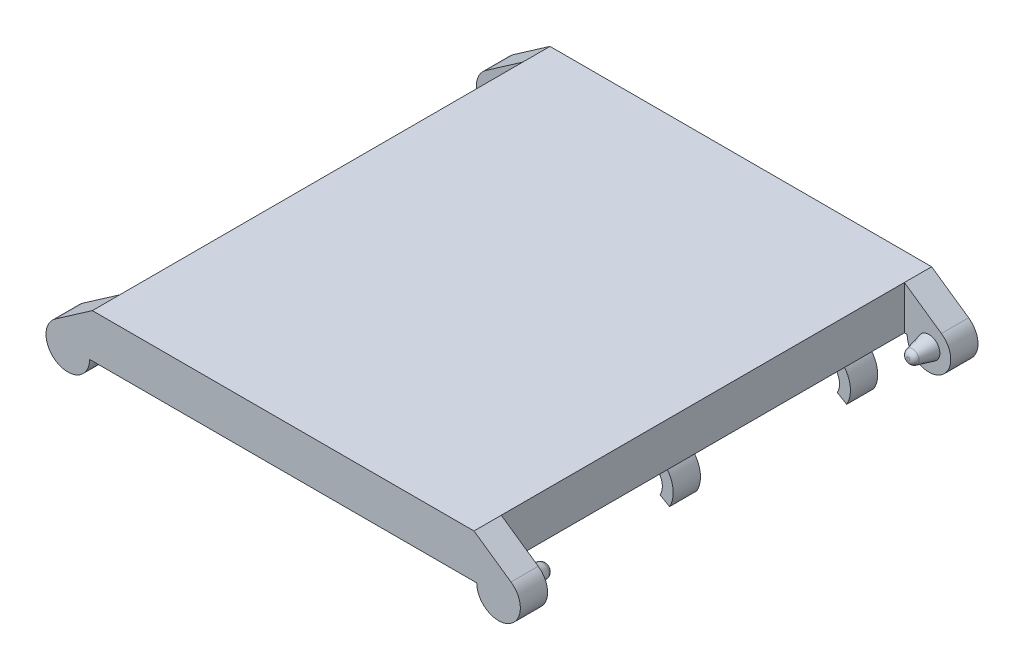
SolidWorks part; units mm, degrees
ref_plane "Front Plane" through (0, 0, 0) normal (0, 0, 1) x (1, 0, 0)
ref_plane "Top Plane" through (0, 0, 0) normal (0, 1, 0) x (1, 0, 0)
ref_plane "Right Plane" through (0, 0, 0) normal (1, 0, 0) x (0, 0, -1)
sketch "Sketch1" plane through (0, 0, 0) normal (0, 1, 0) x (1, 0, 0)
  line L1 (35, -41.97) -> (-35, -41.97)
  line L2 (35, -41.97) -> (35, 41.97)
  line L3 (35, 41.97) -> (-35, 41.97)
  line L4 (-35, -41.97) -> (-35, 41.97)
  line L5 (35, -41.97) -> (-35, 41.97) construction
  line L6 (35, 41.97) -> (-35, -41.97) construction
  point P0 (0, 0)
  dimension "D1" = 70
  dimension "D2" = 83.94
extrude "Boss-Extrude1" add sketch "Sketch1" along normal blind 8
sketch "Sketch3" plane through (0, 0, -41.97) normal (0, 0, -1) x (-1, 0, 0)
  circle A0 centre (-30, -4.1) radius 5.1
  circle A1 centre (30, -4.1) radius 5.1
  circle A2 centre (-30, -4.1) radius 3.1
  circle A3 centre (30, -4.1) radius 3.1
extrude "Boss-Extrude2" add sketch "Sketch3" against normal blind 5 from offset 10 offset against normal yes
ref_plane "Plane1" through (0, 0, -13.22) normal (0, 0, 1) x (1, 0, 0)
mirror "Mirror1" about plane through (0, 0, -13.22) normal (0, 0, 1) of "Boss-Extrude2"
sketch "Sketch4" plane through (0, 0, 5.53) normal (0, 0, 1) x (1, 0, 0)
  line L0 (30, -4.1) -> (40, -9.8735)
  line L1 (40, -9.8735) -> (20, -9.8735)
  line L2 (20, -9.8735) -> (30, -4.1)
  line L3 (0, 0) -> (0, -31.947) construction
  line L4 (-40, -9.8735) -> (-20, -9.8735)
  line L5 (-30, -4.1) -> (-40, -9.8735)
  line L6 (-20, -9.8735) -> (-30, -4.1)
  dimension "D1" = 20
  dimension "D2" = 120
extrude "Cut-Extrude1" cut sketch "Sketch4" against normal blind 63
sketch "Sketch5" plane through (0, 0, 41.97) normal (0, 0, 1) x (1, 0, 0)
  line L0 (35, 8) -> (35.5, 8)
  line L1 (35, 0) -> (41.7832, 4.7157)
  line L2 (35, 0) -> (35, 8)
  arc A0 (41.7832, 4.7157) -> (35.5, 8) centre (39.5, 8) ccw
  circle A1 centre (39.5, 8) radius 4 construction
  dimension "D2" = 8
  dimension "D1" = 4.5
extrude "Boss-Extrude3" add sketch "Sketch5" against normal blind 5 separate body
sketch "Sketch6" plane through (0, 0, 36.97) normal (0, 0, -1) x (-1, 0, 0)
  circle A0 centre (-39.5, 8) radius 2
  dimension "D1" = 4
extrude "Boss-Extrude4" add sketch "Sketch6" along normal blind 3.8 draft 14
fillet "Fillet1" radius 1 1 edges at (38.4474, 8, 33.17)
ref_plane "Plane2" through (0, 4, 0) normal (0, -1, 0) x (-1, 0, 0)
mirror "Mirror2" about plane through (0, 4, 0) normal (0, -1, 0) of bodies 106
delete or keep bodies "Body-Delete/Keep 1" type delete bodies bodies 106
ref_plane "Plane3" through (0, 0, 0) normal (0, 0, 1) x (1, 0, 0)
mirror "Mirror3" about plane through (0, 0, 0) normal (0, 0, 1) of bodies 107
ref_plane "Plane4" through (0, 0, 0) normal (-1, 0, 0) x (0, 0, 1)
mirror "Mirror4" about plane through (0, 0, 0) normal (-1, 0, 0) of bodies 107 108
combine bodies "Combine1" operation type add bodies to combine 110 104 109 107 108
